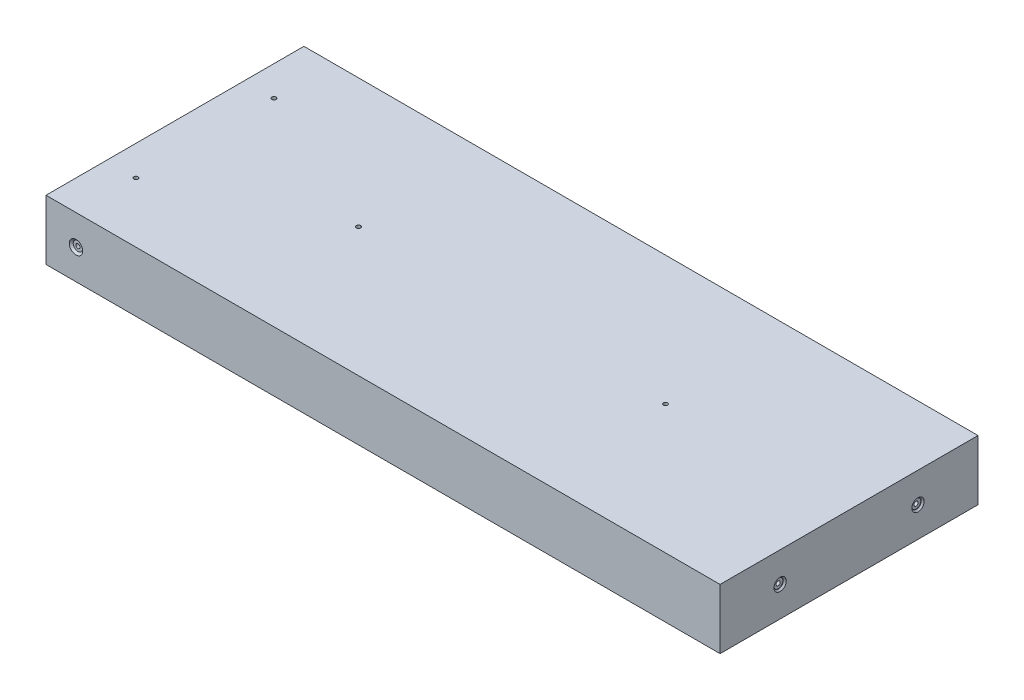
SolidWorks part; units mm, degrees
material "Balsa"
ref_plane "Front Plane" through (0, 0, 0) normal (0, 0, 1) x (1, 0, 0)
ref_plane "Top Plane" through (0, 0, 0) normal (0, 1, 0) x (1, 0, 0)
ref_plane "Right Plane" through (0, 0, 0) normal (1, 0, 0) x (0, 0, -1)
sketch "Sketch1" plane through (0, 0, 0) normal (0, 1, 0) x (1, 0, 0)
  line L1 (-142.7, 54.6) -> (142.7, 54.6)
  line L2 (-142.7, 54.6) -> (-142.7, -54.6)
  line L3 (-142.7, -54.6) -> (142.7, -54.6)
  line L4 (142.7, 54.6) -> (142.7, -54.6)
  line L5 (-142.7, 54.6) -> (142.7, -54.6) construction
  line L6 (-142.7, -54.6) -> (142.7, 54.6) construction
  point P0 (0, 0)
  dimension "D1" = 109.2
  dimension "D2" = 285.4
extrude "Boss-Extrude1" add sketch "Sketch1" along normal blind 25.4
hole_wizard "CBORE for #0 Binding Head Machine Screw1" positions "Sketch2" profile "Sketch3" counterbore size "#0" standard "ANSI Inch"
sketch "Sketch2" plane through (0, 0, 54.6) normal (0, 0, 1) x (1, 0, 0)
  line L0 (-142.7, 25.4) -> (-142.7, 0) construction
  line L1 (-142.7, 25.4) -> (142.7, 25.4) construction
  point P0 (-130, 12.7)
  dimension "D1" = 12.7
  dimension "D2" = 12.7
sketch "Sketch3" plane through (-130, 12.7, 54.6) normal (1, 0, 0) x (0, -1, 0)
  line L0 (0, 0) -> (0, 30.5342)
  line L1 (0, 30.5342) -> (0.889, 30)
  line L2 (0.889, 30) -> (0.889, 0.8128)
  line L3 (0.889, 0.8128) -> (1.985, 0.8128)
  line L5 (1.985, 0.8128) -> (1.985, 0.8725)
  line L6 (1.985, 0.8725) -> (2.8575, 0)
  line L7 (2.8575, 0) -> (0, 0)
  line L8 (-1.985, 0.8725) -> (-2.8575, 0) construction
  line L10 (0, 30.5342) -> (-0.889, 30) construction
  line L11 (0, -6.35) -> (0, 107.95) construction
  dimension "Hole Dia." = 1.778
  dimension "Hole Depth" = 30
  dimension "C'Bore Dia." = 3.97
  dimension "C'Bore Depth" = 0.8128
  dimension "Near C'Sink Dia." = 5.715
  dimension "Near C'Sink Angle" = 90
  dimension "Drill Angle" = 118
mirror "Mirror1" about plane through (0, 0, 0) normal (0, 0, 1) of "CBORE for #0 Binding Head Machine Screw1"
hole_wizard "CBORE for #0 Binding Head Machine Screw2" positions "Sketch4" profile "Sketch5" counterbore size "#0" standard "ANSI Inch"
sketch "Sketch4" plane through (142.7, 0, 0) normal (1, 0, 0) x (0, 0, -1)
  line L0 (-54.6, 25.4) -> (-54.6, 0) construction
  line L2 (-54.6, 25.4) -> (54.6, 25.4) construction
  point P0 (-29.1995, 12.7)
  point P2 (29.2005, 12.7)
  dimension "D1" = 58.4
  dimension "D2" = 25.4005
  dimension "D4" = 12.7
sketch "Sketch5" plane through (142.7, 12.7, 29.1995) normal (0, 1, 0) x (0, 0, -1)
  line L0 (0, 0) -> (0, 30.5342)
  line L1 (0, 30.5342) -> (0.889, 30)
  line L2 (0.889, 30) -> (0.889, 0.8128)
  line L3 (0.889, 0.8128) -> (1.985, 0.8128)
  line L5 (1.985, 0.8128) -> (1.985, 0.635)
  line L6 (1.985, 0.635) -> (2.62, 0)
  line L7 (2.62, 0) -> (0, 0)
  line L8 (-1.985, 0.635) -> (-2.62, 0) construction
  line L10 (0, 30.5342) -> (-0.889, 30) construction
  line L11 (0, -6.35) -> (0, 107.95) construction
  dimension "Hole Dia." = 1.778
  dimension "Hole Depth" = 30
  dimension "C'Bore Dia." = 3.97
  dimension "C'Bore Depth" = 0.8128
  dimension "Near C'Sink Dia." = 5.24
  dimension "Near C'Sink Angle" = 90
  dimension "Drill Angle" = 118
hole_wizard "CBORE for #0 Binding Head Machine Screw4" positions "Sketch8" profile "Sketch9" counterbore size "#0" standard "ANSI Inch"
sketch "Sketch8" plane through (0, 0, 0) normal (0, -1, 0) x (-1, 0, 0)
  line L0 (0, 54.6) -> (0, -54.6) construction
  line L1 (-142.7, 54.6) -> (142.7, 54.6) construction
  line L2 (142.7, -54.6) -> (-142.7, -54.6) construction
  line L4 (142.7, 0) -> (-142.7, 0) construction
  line L5 (142.7, 54.6) -> (142.7, -54.6) construction
  line L6 (-142.7, -54.6) -> (-142.7, 54.6) construction
  point P0 (65, 0)
  point P2 (-65, 0)
  dimension "D1" = 130
sketch "Sketch9" plane through (-65, 0, 0) normal (1, 0, 0) x (0, 0, -1)
  line L0 (0, 0) -> (0, 30.5342)
  line L1 (0, 30.5342) -> (0.889, 30)
  line L2 (0.889, 30) -> (0.889, 0.8128)
  line L3 (0.889, 0.8128) -> (1.985, 0.8128)
  line L5 (1.985, 0.8128) -> (1.985, 0.8725)
  line L6 (1.985, 0.8725) -> (2.8575, 0)
  line L7 (2.8575, 0) -> (0, 0)
  line L8 (-1.985, 0.8725) -> (-2.8575, 0) construction
  line L10 (0, 30.5342) -> (-0.889, 30) construction
  line L11 (0, -6.35) -> (0, 107.95) construction
  dimension "Hole Dia." = 1.778
  dimension "Hole Depth" = 30
  dimension "C'Bore Dia." = 3.97
  dimension "C'Bore Depth" = 0.8128
  dimension "Near C'Sink Dia." = 5.715
  dimension "Near C'Sink Angle" = 90
  dimension "Drill Angle" = 118
hole_wizard "CBORE for #0 Binding Head Machine Screw6" positions "Sketch12" profile "Sketch13" counterbore size "#0" standard "ANSI Inch" end condition through all
sketch "Sketch12" plane through (0, 0, 0) normal (0, -1, 0) x (-1, 0, 0)
  line L0 (142.7, 54.6) -> (142.7, -54.6) construction
  line L1 (-142.7, 54.6) -> (142.7, 54.6) construction
  point P0 (130, 29.2)
  point P2 (130, -29.2)
  dimension "D1" = 12.7
  dimension "D2" = 12.7
  dimension "D3" = 58.4
  dimension "D4" = 25.4
sketch "Sketch13" plane through (-130, 0, -29.2) normal (1, 0, 0) x (0, 0, -1)
  line L0 (0, 0) -> (0, 25.4)
  line L1 (0, 25.4) -> (0.889, 25.4)
  line L3 (0.889, 25.4) -> (0.889, 0.8128)
  line L4 (1.985, 0.8128) -> (0.889, 0.8128)
  line L5 (1.985, 0.8128) -> (1.985, 0.8725)
  line L6 (1.985, 0.8725) -> (2.8575, 0)
  line L7 (2.8575, 0) -> (0, 0)
  line L8 (-1.985, 0.8725) -> (-2.8575, 0) construction
  line L11 (0, -6.35) -> (0, 107.95) construction
  dimension "Thru Hole Dia." = 1.778
  dimension "Thru Hole Depth" = 25.4
  dimension "C'Bore Dia." = 3.97
  dimension "C'Bore Depth" = 0.8128
  dimension "Near C'Sink Dia." = 5.715
  dimension "Near C'Sink Angle" = 90
